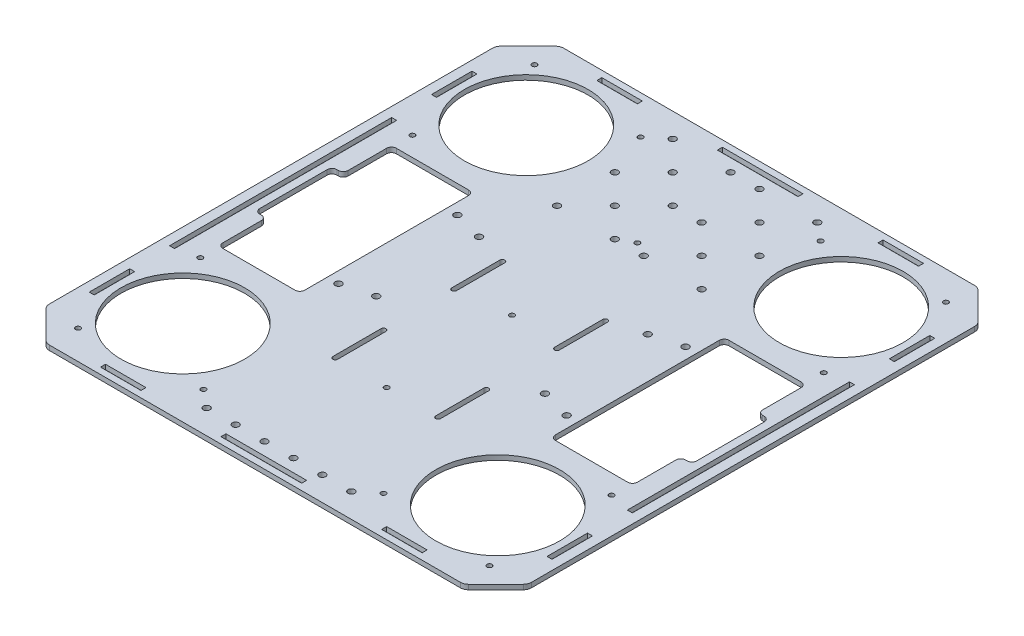
SolidWorks part; units mm, degrees
ref_plane "Front Plane" through (0, 0, 0) normal (0, 0, 1) x (1, 0, 0)
ref_plane "Top Plane" through (0, 0, 0) normal (0, 1, 0) x (1, 0, 0)
ref_plane "Right Plane" through (0, 0, 0) normal (1, 0, 0) x (0, 0, -1)
sketch "Sketch1" plane through (0, 0, 0) normal (0, 1, 0) x (1, 0, 0)
  line L0 (0, 0) -> (16.6467, 0) construction
  line L1 (0, 0) -> (0, 19.1715) construction
  line L3 (150, 137.9289) -> (150, 56.0767)
  line L4 (129, 54) -> (78, 54)
  line L7 (32, -50) -> (68, -50) construction
  line L8 (32, -50) -> (32, 50) construction
  line L9 (32, 50) -> (68, 50) construction
  line L10 (68, -50) -> (68, 50) construction
  line L11 (32, -50) -> (68, 50) construction
  line L12 (32, 50) -> (68, -50) construction
  line L20 (131.4645, 158.5355) -> (148.5355, 141.4645)
  line L21 (78, 54) -> (78, -54)
  line L23 (127.9289, 160) -> (-127.9289, 160)
  line L24 (129, -54) -> (78, -54)
  line L25 (150, -137.9289) -> (150, -55.9233)
  line L26 (131.4645, -158.5355) -> (148.5355, -141.4645)
  line L27 (127.9289, -160) -> (-127.9289, -160)
  line L28 (-131.4645, 158.5355) -> (-148.5355, 141.4645)
  line L29 (-150, 137.9289) -> (-150, 56.0767)
  line L33 (-150, -137.9289) -> (-150, -55.9233)
  line L34 (-131.4645, -158.5355) -> (-148.5355, -141.4645)
  line L36 (150, 56.0767) -> (150, -55.9233)
  line L38 (-129, 54) -> (-78, 54)
  line L40 (-78, 54) -> (-78, -54)
  line L41 (-150, 56.0767) -> (-150, -55.9233)
  line L42 (-129, -54) -> (-78, -54)
  line L47 (129, 54) -> (129, 24)
  line L48 (129, 24) -> (136, 24)
  line L49 (136, 24) -> (136, -24)
  line L50 (129, -54) -> (129, -24)
  line L51 (129, -24) -> (136, -24)
  line L52 (-129, -54) -> (-129, -24)
  line L53 (-129, -24) -> (-136, -24)
  line L54 (-136, 24) -> (-136, -24)
  line L55 (-129, 24) -> (-136, 24)
  line L56 (-129, 54) -> (-129, 24)
  circle A5 centre (52.5, 32) radius 2.075
  circle A7 centre (52.5, -32) radius 2.075
  circle A8 centre (-52.5, -32) radius 2.075
  circle A9 centre (-52.5, 32) radius 2.075
  arc A10 (131.4645, -158.5355) -> (127.9289, -160) centre (127.9289, -155) cw
  arc A11 (150, -137.9289) -> (148.5355, -141.4645) centre (145, -137.9289) cw
  arc A12 (-131.4645, -158.5355) -> (-127.9289, -160) centre (-127.9289, -155) ccw
  arc A13 (-150, -137.9289) -> (-148.5355, -141.4645) centre (-145, -137.9289) ccw
  arc A18 (148.5355, 141.4645) -> (150, 137.9289) centre (145, 137.9289) cw
  arc A19 (131.4645, 158.5355) -> (127.9289, 160) centre (127.9289, 155) ccw
  arc A20 (-148.5355, 141.4645) -> (-150, 137.9289) centre (-145, 137.9289) ccw
  arc A21 (-131.4645, 158.5355) -> (-127.9289, 160) centre (-127.9289, 155) cw
  circle A22 centre (0, 0) radius 145 construction
  circle A23 centre (-98, 106.8691) radius 38.5
  circle A24 centre (98, 106.8691) radius 38.5
  circle A25 centre (-98, -106.8691) radius 38.5
  circle A26 centre (98, -106.8691) radius 38.5
  circle A27 centre (-71, 37) radius 2.075
  circle A28 centre (-71, -37) radius 2.075
  circle A29 centre (71, 37) radius 2.075
  circle A30 centre (71, -37) radius 2.075
  point P16 (-144, 52)
  point P17 (50, 0)
  point P18 (-144, -52)
  point P31 (78, 0)
  point P33 (78, 0)
  point P38 (0, 150)
  point P41 (0, 160)
  point P43 (0, -150)
  point P50 (0, -160)
  point P52 (130, -160)
  point P55 (150, -140)
  point P58 (-130, -160)
  point P61 (-150, -140)
  point P64 (-150, -54)
  point P67 (-150, 54)
  point P70 (150, 54)
  point P73 (150, -54)
  point P76 (150, 140)
  point P79 (130, 160)
  point P82 (-150, 140)
  point P85 (-130, 160)
  point P87 (144, -52)
  point P95 (136, 0)
  dimension "D2" = 290
  dimension "D3" = 160
  dimension "D9" = 15.5
  dimension "D10" = 32
  dimension "D11" = 4.15
  dimension "D12" = 10
  dimension "D15" = 5
  dimension "D16" = 77
  dimension "D17" = 98
  dimension "D18" = 24
  dimension "D19" = 21
  dimension "D21" = 37
  dimension "D22" = 58
  dimension "D23" = 71
  dimension "D4" = 150
  dimension "D5" = 54
  dimension "D6" = 32
  dimension "D7" = 100
  dimension "D8" = 36
  dimension "D13" = 135
  dimension "D14" = 20
  dimension "D20" = 14
base flange "Base-Flange1" sketch "Sketch1" thickness 3 reverse thickness direction no parameters "D1"=0.7366
sketch "Sketch6" plane through (0, 0, 0) normal (0, 1, 0) x (1, 0, 0)
  line L0 (0, 0) -> (17.8088, 0) construction
  line L1 (0, 0) -> (0, 40.1375) construction
  line L2 (74.9, 156) -> (74.9, 152.9)
  line L3 (133.5, 54) -> (133.5, -54) construction
  line L4 (-32, -78) -> (-32, -48) construction
  line L5 (129, -54) -> (78, -54) construction
  line L6 (78, 54) -> (129, 54) construction
  line L7 (140.9, 54) -> (140.9, 69.1)
  line L8 (140.9, 69.1) -> (144, 69.1)
  line L11 (140.9, 119.1) -> (140.9, 93.9)
  line L12 (140.9, 93.9) -> (144, 93.9)
  line L13 (144, 93.9) -> (144, 119.1)
  line L14 (144, 119.1) -> (140.9, 119.1)
  line L15 (74.9, 152.9) -> (100.1, 152.9)
  line L16 (100.1, 152.9) -> (100.1, 156)
  line L17 (-25.1, 156) -> (25.1, 156)
  line L18 (25.1, 156) -> (25.1, 152.9)
  line L19 (25.1, 152.9) -> (-25.1, 152.9)
  line L20 (100.1, 156) -> (74.9, 156)
  line L21 (127.9289, 160) -> (-127.9289, 160) construction
  line L22 (-25.1, 156) -> (-25.1, 152.9)
  line L23 (150, -137.9289) -> (150, 137.9289) construction
  line L24 (-100.1, 152.9) -> (-100.1, 156)
  line L25 (-74.9, 152.9) -> (-100.1, 152.9)
  line L26 (-74.9, 156) -> (-74.9, 152.9)
  line L27 (-100.1, 156) -> (-74.9, 156)
  line L28 (-144, 69.1) -> (-144, 54)
  line L29 (-140.9, 69.1) -> (-144, 69.1)
  line L30 (-140.9, 54) -> (-140.9, 69.1)
  line L32 (-144, 93.9) -> (-144, 119.1)
  line L33 (-140.9, 93.9) -> (-144, 93.9)
  line L34 (-140.9, 119.1) -> (-140.9, 93.9)
  line L35 (-144, 119.1) -> (-140.9, 119.1)
  line L36 (-140.9, -69.1) -> (-144, -69.1)
  line L37 (-140.9, -54) -> (-140.9, -69.1)
  line L39 (-144, -69.1) -> (-144, -54)
  line L40 (-140.9, -93.9) -> (-144, -93.9)
  line L41 (-140.9, -119.1) -> (-140.9, -93.9)
  line L42 (-144, -119.1) -> (-140.9, -119.1)
  line L43 (-144, -93.9) -> (-144, -119.1)
  line L44 (144, -69.1) -> (144, -54)
  line L45 (140.9, -69.1) -> (144, -69.1)
  line L46 (140.9, -54) -> (140.9, -69.1)
  line L48 (144, -93.9) -> (144, -119.1)
  line L49 (140.9, -93.9) -> (144, -93.9)
  line L50 (140.9, -119.1) -> (140.9, -93.9)
  line L51 (144, -119.1) -> (140.9, -119.1)
  line L52 (100.1, -152.9) -> (100.1, -156)
  line L53 (74.9, -152.9) -> (100.1, -152.9)
  line L54 (74.9, -156) -> (74.9, -152.9)
  line L55 (100.1, -156) -> (74.9, -156)
  line L56 (-74.9, -152.9) -> (-100.1, -152.9)
  line L57 (-74.9, -156) -> (-74.9, -152.9)
  line L58 (-100.1, -156) -> (-74.9, -156)
  line L59 (-100.1, -152.9) -> (-100.1, -156)
  line L60 (25.1, -156) -> (25.1, -152.9)
  line L61 (-25.1, -156) -> (25.1, -156)
  line L62 (-25.1, -156) -> (-25.1, -152.9)
  line L63 (25.1, -152.9) -> (-25.1, -152.9)
  line L64 (150, -137.9289) -> (150, 137.9289) construction
  line L67 (-33.5, -78) -> (-33.5, -48)
  line L68 (-30.5, -78) -> (-30.5, -48)
  line L69 (32, -78) -> (32, -48) construction
  line L70 (33.5, -78) -> (33.5, -48)
  line L71 (30.5, -78) -> (30.5, -48)
  line L72 (-32, -4) -> (-32, 26) construction
  line L73 (-33.5, -4) -> (-33.5, 26)
  line L74 (-30.5, -4) -> (-30.5, 26)
  line L75 (32, -4) -> (32, 26) construction
  line L78 (33.5, -4) -> (33.5, 26)
  line L79 (30.5, -4) -> (30.5, 26)
  line L80 (-27, -70) -> (-27, -50) construction
  line L81 (140.9, 54) -> (140.9, -54)
  line L82 (144, -54) -> (144, 54)
  line L83 (-140.9, 54) -> (-140.9, -54)
  line L84 (-144, -54) -> (-144, 54)
  line L85 (144, 69.1) -> (144, 54)
  line L86 (-28.5, -70) -> (-28.5, -50) construction
  line L87 (-25.5, -70) -> (-25.5, -50) construction
  line L88 (-27, 22) -> (-27, 42) construction
  line L89 (-28.5, 22) -> (-28.5, 42) construction
  line L90 (-25.5, 22) -> (-25.5, 42) construction
  line L91 (27, 22) -> (27, 42) construction
  line L92 (28.5, 22) -> (28.5, 42) construction
  line L93 (25.5, 22) -> (25.5, 42) construction
  line L94 (27, -70) -> (27, -50) construction
  line L95 (28.5, -70) -> (28.5, -50) construction
  line L96 (25.5, -70) -> (25.5, -50) construction
  circle A1 centre (0, 0) radius 145 construction
  circle A2 centre (128, 142) radius 1.55
  circle A3 centre (-56, 136) radius 1.55
  circle A4 centre (-128, 142) radius 1.55
  circle A5 centre (128, 66) radius 1.55
  circle A8 centre (56, 136) radius 1.55
  circle A9 centre (-128, -142) radius 1.55
  circle A10 centre (128, -66) radius 1.55
  circle A11 centre (128, -142) radius 1.55
  circle A12 centre (0, 78) radius 1.55
  circle A13 centre (0, -78) radius 1.55
  circle A14 centre (56, -136) radius 1.55
  circle A15 centre (-56, -136) radius 1.55
  circle A16 centre (-128, 66) radius 1.55
  circle A17 centre (-128, -66) radius 1.55
  circle A18 centre (52.5, 32) radius 2.075 construction
  circle A20 centre (32, -48) radius 1.55 construction
  circle A21 centre (-32, 26) radius 1.55 construction
  circle A22 centre (-32, -48) radius 1.55 construction
  arc A25 (-33.5, -78) -> (-30.5, -78) centre (-32, -78) ccw
  arc A26 (-30.5, -48) -> (-33.5, -48) centre (-32, -48) ccw
  arc A27 (33.5, -78) -> (30.5, -78) centre (32, -78) cw
  arc A28 (30.5, -48) -> (33.5, -48) centre (32, -48) cw
  arc A29 (-33.5, -4) -> (-30.5, -4) centre (-32, -4) ccw
  arc A30 (-30.5, 26) -> (-33.5, 26) centre (-32, 26) ccw
  circle A33 centre (0, 0) radius 1.55
  circle A36 centre (122.9, 136.9) radius 1.55 construction
  arc A40 (33.5, -4) -> (30.5, -4) centre (32, -4) cw
  arc A41 (30.5, 26) -> (33.5, 26) centre (32, 26) cw
  circle A42 centre (32, 26) radius 1.55 construction
  circle A43 centre (-122.9, 136.9) radius 1.55 construction
  circle A44 centre (122.9, -136.9) radius 1.55 construction
  circle A45 centre (-122.9, -136.9) radius 1.55 construction
  arc A46 (-28.5, -70) -> (-25.5, -70) centre (-27, -70) ccw construction
  arc A47 (-25.5, -50) -> (-28.5, -50) centre (-27, -50) ccw construction
  arc A48 (-28.5, 22) -> (-25.5, 22) centre (-27, 22) ccw construction
  arc A49 (-25.5, 42) -> (-28.5, 42) centre (-27, 42) ccw construction
  arc A50 (28.5, 22) -> (25.5, 22) centre (27, 22) cw construction
  arc A51 (25.5, 42) -> (28.5, 42) centre (27, 42) cw construction
  arc A52 (28.5, -70) -> (25.5, -70) centre (27, -70) cw construction
  arc A53 (25.5, -50) -> (28.5, -50) centre (27, -50) cw construction
  point P47 (0, 152.9)
  point P48 (0, 156)
  point P117 (-32, -63)
  point P124 (32, -63)
  point P131 (-32, 11)
  point P138 (32, 11)
  point P154 (-27, -60)
  point P159 (-27, 32)
  point P168 (27, 32)
  point P175 (27, -60)
  dimension "D2" = 290
  dimension "D13" = 18
  dimension "D14" = 3.1
  dimension "D15" = 76
  dimension "D16" = 5.1
  dimension "D17" = 22
  dimension "D12" = 72
  dimension "D18" = 78
  dimension "D19" = 30
  dimension "D4" = 81
  dimension "D20" = 3.1
  dimension "D21" = 32
  dimension "D27" = 74
  dimension "D29" = 6
  dimension "D31" = 69.1
  dimension "D30" = 30
  dimension "D25" = 5.1
  dimension "D28" = 3.1
  dimension "D26" = 4
  dimension "D32" = 64
  dimension "D33" = 128
  dimension "D34" = 1.5
  dimension "D38" = 50
  dimension "D5" = 6
  dimension "D6" = 25.2
  dimension "D7" = 24.8
  dimension "D8" = 25.2
  dimension "D9" = 25.1
  dimension "D10" = 49.8
  dimension "D11" = 4
  dimension "D22" = 3.1
  dimension "D35" = 20
  dimension "D36" = 92
  dimension "D37" = 27
extrude "Cut-Extrude1" cut sketch "Sketch6" against normal blind 10 normal cut yes
fillet "Fillet1" radius 3 16 edges at (136, -1.5, 24) (136, -1.5, -24) (-136, -1.5, -24) (-136, -1.5, 24) (-129, -1.5, 24) (-129, -1.5, -24) (129, -1.5, 24) (129, -1.5, -24) (78, -1.5, -54) (129, -1.5, -54) (129, -1.5, 54) (78, -1.5, 54) (-129, -1.5, 54) (-78, -1.5, 54) (-78, -1.5, -54) (-129, -1.5, -54)
sketch "Sketch7" plane through (0, 0, 0) normal (0, 1, 0) x (1, 0, 0)
  line L0 (0, -28.1115) -> (0, 34.5988) construction
  line L1 (21.8044, 0) -> (-11.3527, 0) construction
  line L2 (-127.9289, -160) -> (127.9289, -160) construction
  line L4 (-45.5, -132) -> (45.5, -132) construction
  line L5 (-60, -117.5) -> (-60, -107.5) construction
  line L6 (-45.5, -93) -> (45.5, -93) construction
  line L7 (60, -117.5) -> (60, -107.5) construction
  line L8 (-60, -132) -> (60, -93) construction
  line L9 (-60, -93) -> (60, -132) construction
  circle A0 centre (-27, -145) radius 2.05
  circle A1 centre (-9, -145) radius 2.05
  circle A2 centre (-45, -145) radius 2.05
  circle A3 centre (45, -145) radius 2.05
  circle A4 centre (27, -145) radius 2.05
  circle A5 centre (9, -145) radius 2.05
  circle A6 centre (9, 145) radius 2.05
  circle A7 centre (27, 145) radius 2.05 construction
  circle A8 centre (45, 145) radius 2.05
  circle A9 centre (-45, 145) radius 2.05
  circle A10 centre (-9, 145) radius 2.05
  circle A11 centre (-27, 145) radius 2.05 construction
  arc A12 (-45.5, -132) -> (-60, -117.5) centre (-45.5, -117.5) cw construction
  arc A13 (-60, -107.5) -> (-45.5, -93) centre (-45.5, -107.5) cw construction
  arc A14 (45.5, -132) -> (60, -117.5) centre (45.5, -117.5) ccw construction
  arc A15 (45.5, -93) -> (60, -107.5) centre (45.5, -107.5) cw construction
  circle A17 centre (9, 127) radius 2.05 construction
  circle A18 centre (27, 127) radius 2.05
  circle A19 centre (45, 127) radius 2.05 construction
  circle A24 centre (9, 109) radius 2.05
  circle A25 centre (27, 109) radius 2.05 construction
  circle A26 centre (45, 109) radius 2.05
  circle A27 centre (27, 91) radius 2.05
  circle A28 centre (9, 91) radius 2.05 construction
  circle A29 centre (45, 91) radius 2.05 construction
  circle A30 centre (-45, 91) radius 2.05 construction
  circle A31 centre (-9, 91) radius 2.05 construction
  circle A32 centre (-27, 91) radius 2.05
  circle A33 centre (-45, 109) radius 2.05
  circle A34 centre (-27, 109) radius 2.05 construction
  circle A35 centre (-9, 109) radius 2.05
  circle A36 centre (-45, 127) radius 2.05 construction
  circle A37 centre (-27, 127) radius 2.05
  circle A38 centre (-9, 127) radius 2.05 construction
  circle A39 centre (45, 73) radius 2.05
  circle A40 centre (9, 73) radius 2.05
  circle A41 centre (-9, 73) radius 2.05
  circle A42 centre (-45, 73) radius 2.05
  point P11 (0, -112.5)
  dimension "D1" = 9
  dimension "D2" = 27
  dimension "D3" = 45
  dimension "D4" = 15
  dimension "D5" = 4.1
  dimension "D9" = 14.5
  dimension "D10" = 18
  dimension "D11" = 18
  dimension "D12" = 18
  dimension "D13" = 18
  dimension "D6" = 28
  dimension "D7" = 39
  dimension "D8" = 60
extrude "Cut-Extrude2" cut sketch "Sketch7" against normal blind 10 normal cut yes
sketch "Sketch8" plane through (0, 0, 0) normal (0, 1, 0) x (1, 0, 0)
  line L0 (100.1, 156) -> (125.1, 156) construction
  line L1 (0, 0) -> (128, 142) construction
  line L2 (40.1919, 0) -> (-35.5801, 0) construction
  line L3 (144, 119.1) -> (144, 137.1) construction
  line L4 (125.1, 156) -> (144, 137.1) construction
  line L11 (0, 198.7378) -> (0, 88.7197) construction
  line L12 (100.1, 156) -> (74.9, 156) construction
  circle A0 centre (128, 142) radius 1.55 construction
  circle A1 centre (128, 142) radius 1.55 construction
  dimension "D1" = 135
  dimension "D2" = 25
  dimension "D3" = 18
  dimension "D4" = 125.1
  dimension "D5" = 137.1
  dimension "D6" = 144
  dimension "D7" = 156
sketch "Bend-Lines1" [suppressed] plane through (0, 0, 0) normal (0, 1, 0) x (1, 0, 0)
sketch "Bounding-Box1" [suppressed] plane through (0, 0, 0) normal (0, 1, 0) x (1, 0, 0)
sheet metal parameters "Sheet-Metal2" thickness 3 parameters "D1"=0.7366
flat pattern "Flat-Pattern2" [suppressed]
sketch "Bend-Lines2" plane through (0, 0, 0) normal (0, 1, 0) x (1, 0, 0)
sketch3d "Bounding-Box2" [suppressed]
  line L0 (2.0001, -205.9999, 0) -> (2, 94, 0) construction
  line L1 (-267.9999, -206, 0) -> (-268, 93.9999, 0) construction
  line L2 (2.0001, -205.9999, 0) -> (-267.9999, -206, 0) construction
  line L3 (2, 94, 0) -> (-268, 93.9999, 0) construction
sheet metal parameters "Sheet-Metal4" thickness 3 parameters "D1"=0.7366
flat pattern "Flat-Pattern2"
sketch "Bend-Lines2" plane through (0, 0, 0) normal (0, 1, 0) x (1, 0, 0)
sketch3d "Bounding-Box2" [suppressed]
  line L0 (22.0712, -4.9999, 0) -> (22.0711, 315, 0) construction
  line L1 (-277.9288, -5, 0) -> (-277.9289, 314.9999, 0) construction
  line L2 (22.0712, -4.9999, 0) -> (-277.9288, -5, 0) construction
  line L3 (22.0711, 315, 0) -> (-277.9289, 314.9999, 0) construction
sheet metal parameters "Sheet-Metal5" thickness 3 parameters "D1"=0.7366
flat pattern "Flat-Pattern2"
sketch "Bend-Lines2" plane through (0, 0, 0) normal (0, 1, 0) x (1, 0, 0)
sketch3d "Bounding-Box2" [suppressed]
  line L0 (22.0712, -4.9999, 0) -> (22.0711, 315, 0) construction
  line L1 (-277.9288, -5, 0) -> (-277.9289, 314.9999, 0) construction
  line L2 (22.0712, -4.9999, 0) -> (-277.9288, -5, 0) construction
  line L3 (22.0711, 315, 0) -> (-277.9289, 314.9999, 0) construction
